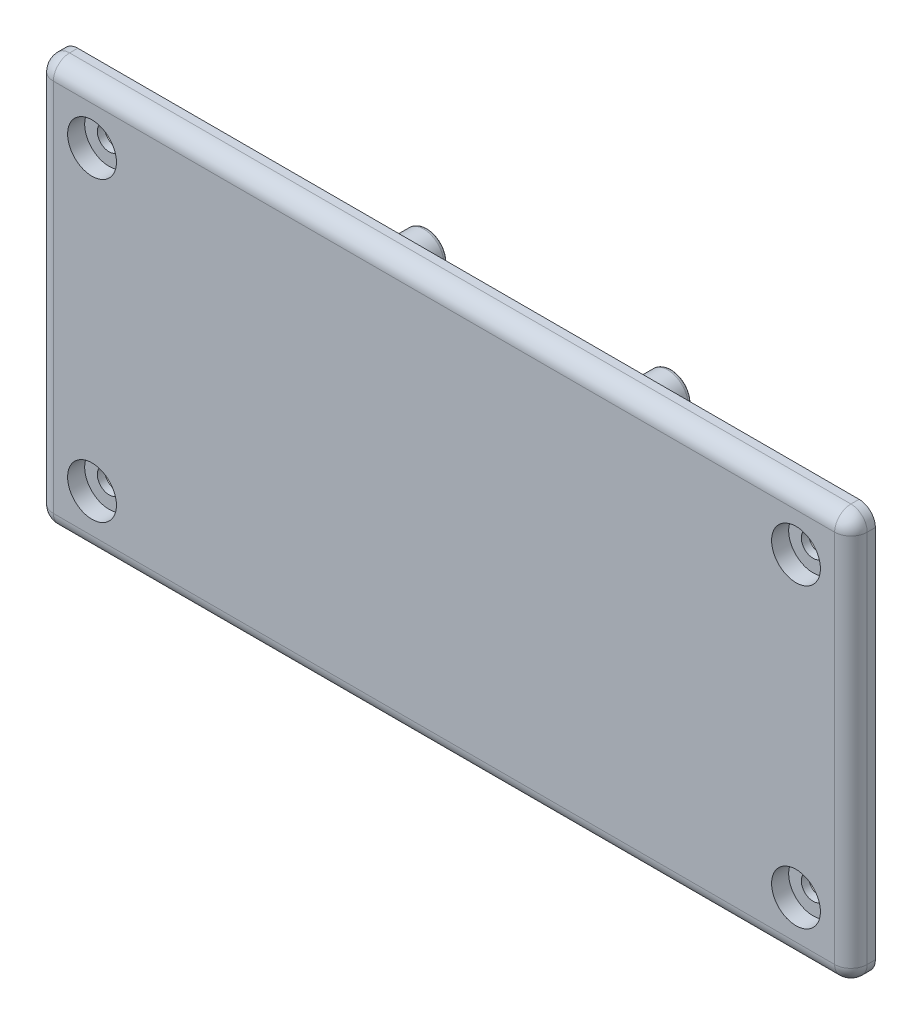
SolidWorks part; units mm, degrees
ref_plane "Front Plane" through (0, 0, 0) normal (0, 0, 1) x (1, 0, 0)
ref_plane "Top Plane" through (0, 0, 0) normal (0, 1, 0) x (1, 0, 0)
ref_plane "Right Plane" through (0, 0, 0) normal (1, 0, 0) x (0, 0, -1)
sketch "Sketch1" plane through (0, 0, 0) normal (0, 0, 1) x (1, 0, 0)
  line L4 (-48, -25) -> (48, -25)
  line L5 (50, -23) -> (50, 23)
  line L6 (48, 25) -> (-48, 25)
  line L7 (-50, 23) -> (-50, -23)
  line L8 (-48, -25) -> (48, -25)
  line L9 (50, -23) -> (50, 23)
  line L10 (48, 25) -> (-48, 25)
  line L11 (-50, 23) -> (-50, -23)
  arc A4 (48, -25) -> (50, -23) centre (48, -23) ccw
  arc A5 (50, 23) -> (48, 25) centre (48, 23) ccw
  arc A6 (-48, 25) -> (-50, 23) centre (-48, 23) ccw
  arc A7 (-50, -23) -> (-48, -25) centre (-48, -23) ccw
  arc A8 (48, -25) -> (50, -23) centre (48, -23) ccw
  arc A9 (50, 23) -> (48, 25) centre (48, 23) ccw
  arc A10 (-48, 25) -> (-50, 23) centre (-48, 23) ccw
  arc A11 (-50, -23) -> (-48, -25) centre (-48, -23) ccw
  dimension "D1" = 0
extrude "Boss-Extrude1" add sketch "Sketch1" along normal blind 3
fillet "Fillet1" radius 2 8 edges at (-50, 0, 3) (-49.4142, 24.4142, 3) (0, 25, 3) (49.4142, 24.4142, 3) (50, 0, 3) (49.4142, -24.4142, 3) (0, -25, 3) (-49.4142, -24.4142, 3)
sketch "Sketch2" plane through (0, 0, 0) normal (0, 0, -1) x (-1, 0, 0)
  line L0 (-25, -18.5) -> (-25, -21.5)
  line L1 (-35, -18.5) -> (-35, -21.5)
  line L2 (25, -18.5) -> (25, -21.5)
  line L3 (35, -18.5) -> (35, -21.5)
  line L4 (50, -23) -> (50, 23)
  line L5 (48, 25) -> (-48, 25)
  line L6 (-50, 23) -> (-50, -23)
  line L7 (-48, -25) -> (48, -25)
  line L8 (50, -23) -> (50, 23)
  line L9 (48, 25) -> (-48, 25)
  line L10 (-50, 23) -> (-50, -23)
  line L11 (-48, -25) -> (48, -25)
  line L12 (50, -23) -> (50, 23)
  line L13 (48, 25) -> (-48, 25)
  line L14 (-50, 23) -> (-50, -23)
  line L15 (-48, -25) -> (48, -25)
  line L16 (50, -23) -> (50, 23)
  line L17 (48, 25) -> (-48, 25)
  line L18 (-50, 23) -> (-50, -23)
  line L19 (-48, -25) -> (48, -25)
  line L20 (25, 18.5) -> (25, 21.5)
  line L21 (35, 18.5) -> (35, 21.5)
  line L22 (43.5, -10) -> (46.5, -10)
  line L23 (43.5, 10) -> (46.5, 10)
  line L24 (-46.5, -21.5) -> (46.5, -21.5)
  line L25 (-46.5, 21.5) -> (-46.5, -21.5)
  line L26 (46.5, 21.5) -> (-46.5, 21.5)
  line L27 (46.5, -21.5) -> (46.5, 21.5)
  line L28 (-46.5, -21.5) -> (46.5, -21.5)
  line L29 (-46.5, 21.5) -> (-46.5, -21.5)
  line L30 (46.5, 21.5) -> (-46.5, 21.5)
  line L31 (46.5, -21.5) -> (46.5, 21.5)
  line L32 (43.5, -18.5) -> (43.5, 18.5)
  line L33 (43.5, 18.5) -> (-43.5, 18.5)
  line L34 (-43.5, 18.5) -> (-43.5, -18.5)
  line L35 (-43.5, -18.5) -> (43.5, -18.5)
  line L36 (-43.5, -10) -> (-43.5, 10)
  line L37 (-25, 18.5) -> (-35, 18.5)
  line L38 (-43.5, 10) -> (-46.5, 10)
  line L39 (-43.5, 10) -> (-43.5, -10)
  line L40 (-43.5, -10) -> (-46.5, -10)
  line L41 (-46.5, 10) -> (-46.5, -10)
  line L42 (43.5, 0) -> (-46.5, 0) construction
  line L43 (-25, 18.5) -> (-35, 18.5)
  line L44 (-25, 18.5) -> (-25, 21.5)
  line L45 (-25, 21.5) -> (-35, 21.5)
  line L46 (-35, 18.5) -> (-35, 21.5)
  line L47 (0, 18.5) -> (0, -18.5) construction
  arc A4 (48, -25) -> (50, -23) centre (48, -23) ccw
  arc A5 (50, 23) -> (48, 25) centre (48, 23) ccw
  arc A6 (-48, 25) -> (-50, 23) centre (-48, 23) ccw
  arc A7 (-50, -23) -> (-48, -25) centre (-48, -23) ccw
  arc A8 (48, -25) -> (50, -23) centre (48, -23) ccw
  arc A9 (50, 23) -> (48, 25) centre (48, 23) ccw
  arc A10 (-48, 25) -> (-50, 23) centre (-48, 23) ccw
  arc A11 (-50, -23) -> (-48, -25) centre (-48, -23) ccw
  arc A12 (50, 23) -> (48, 25) centre (48, 23) ccw
  arc A13 (-48, 25) -> (-50, 23) centre (-48, 23) ccw
  arc A14 (-50, -23) -> (-48, -25) centre (-48, -23) ccw
  arc A15 (48, -25) -> (50, -23) centre (48, -23) ccw
  arc A16 (50, 23) -> (48, 25) centre (48, 23) ccw
  arc A17 (-48, 25) -> (-50, 23) centre (-48, 23) ccw
  arc A18 (-50, -23) -> (-48, -25) centre (-48, -23) ccw
  arc A19 (48, -25) -> (50, -23) centre (48, -23) ccw
  point P24 (-43.5, 0)
  point P29 (-30, 18.5)
  dimension "D5" = 20
  dimension "D6" = 10
  dimension "D7" = 11.5
  dimension "D1" = 0
  dimension "D2" = 0
  dimension "D3" = 3.5
  dimension "D4" = 3
extrude "Boss-Extrude2" add sketch "Sketch2" along normal blind 1.5 contours L46 L33 L44 L30 | L40 L34 L38 L29 | L35 L1 L28 L0 | L35 L2 L28 L3 | L32 L22 L31 L23 | L33 L21 L30 L20 region at (30, -20, 0) region at (-30, -20, 0) region at (45, 0, 0) region at (-45, 0, 0) region at (30, 20, 0) region at (-30, 20, 0)
fillet "Fillet2" radius 1 48 edges at (-25, 20, -1.5) (-30, 21.5, -1.5) (-35, 20, -1.5) (-30, 18.5, -1.5) (-35, -20, -1.5) (-30, -21.5, -1.5) (-25, -20, -1.5) (-30, -18.5, -1.5) (-45, 10, -1.5) (-46.5, 0, -1.5) (-45, -10, -1.5) (-43.5, 0, -1.5) (25, -20, -1.5) (30, -21.5, -1.5) (35, -20, -1.5) (30, -18.5, -1.5) (46.5, 0, -1.5) (45, 10, -1.5) (43.5, 0, -1.5) (45, -10, -1.5) (30, 21.5, -1.5) (25, 20, -1.5) (30, 18.5, -1.5) (35, 20, -1.5) (-25, 21.5, -0.75) (-35, 21.5, -0.75) (-35, 18.5, -0.75) (-25, 18.5, -0.75) (-25, -18.5, -0.75) (-25, -21.5, -0.75) (-35, -21.5, -0.75) (-35, -18.5, -0.75) (-46.5, -10, -0.75) (-43.5, -10, -0.75) (-46.5, 10, -0.75) (-43.5, 10, -0.75) (25, -18.5, -0.75) (25, -21.5, -0.75) (35, -18.5, -0.75) (35, -21.5, -0.75) (25, 21.5, -0.75) (25, 18.5, -0.75) (35, 21.5, -0.75) (35, 18.5, -0.75) (43.5, 10, -0.75) (46.5, 10, -0.75) (46.5, -10, -0.75) (43.5, -10, -0.75)
sketch "Sketch3" plane through (0, 0, 0) normal (0, 0, -1) x (-1, 0, 0)
  line L4 (50, -23) -> (50, 23)
  line L5 (48, 25) -> (-48, 25)
  line L6 (-50, 23) -> (-50, -23)
  line L7 (-48, -25) -> (48, -25)
  line L8 (50, -23) -> (50, 23)
  line L9 (48, 25) -> (-48, 25)
  line L10 (-50, 23) -> (-50, -23)
  line L11 (-48, -25) -> (48, -25)
  circle A0 centre (-15, -15) radius 3.0099 construction
  circle A1 centre (-15, 15) radius 3.0099 construction
  circle A2 centre (15, -15) radius 3.0099 construction
  circle A3 centre (15, 15) radius 3.0099 construction
  arc A4 (48, -25) -> (50, -23) centre (48, -23) ccw
  arc A5 (50, 23) -> (48, 25) centre (48, 23) ccw
  arc A6 (-48, 25) -> (-50, 23) centre (-48, 23) ccw
  arc A7 (-50, -23) -> (-48, -25) centre (-48, -23) ccw
  arc A8 (48, -25) -> (50, -23) centre (48, -23) ccw
  arc A9 (50, 23) -> (48, 25) centre (48, 23) ccw
  arc A10 (-48, 25) -> (-50, 23) centre (-48, 23) ccw
  arc A11 (-50, -23) -> (-48, -25) centre (-48, -23) ccw
  circle A12 centre (-15, -15) radius 3.0099 construction
  circle A13 centre (-15, 15) radius 3.0099 construction
  circle A14 centre (15, -15) radius 3.0099 construction
  circle A15 centre (15, 15) radius 3.0099 construction
  circle A16 centre (-15, 15) radius 2.5099
  circle A17 centre (-15, -15) radius 2.5099
  circle A18 centre (15, -15) radius 2.5099
  circle A19 centre (15, 15) radius 2.5099
  dimension "D1" = 0
  dimension "D2" = 0.5
extrude "Boss-Extrude3" add sketch "Sketch3" along normal blind 10 contours A17 | A16 | A18 | A19 region at (15, 15, 0) region at (15, -15, 0) region at (-15, -15, 0) region at (-15, 15, 0)
fillet "Fillet3" radius 0.5 4 edges at (12.4901, 15, -10) (-17.5099, -15, -10) (-17.5099, 15, -10) (12.4901, -15, -10)
sketch "Sketch4" plane through (0, 0, 3) normal (0, 0, 1) x (1, 0, 0)
  line L0 (-47, 14.5) -> (-39.5001, 14.5) construction
  line L1 (-39.5001, 22) -> (-39.5001, 14.5) construction
  line L2 (47, -14.5) -> (39.5001, -14.5) construction
  line L3 (39.5001, -22) -> (39.5001, -14.5) construction
  line L4 (48, 23) -> (-48, 23)
  line L5 (-48, 23) -> (-48, -23)
  line L6 (-48, -23) -> (48, -23)
  line L7 (48, -23) -> (48, 23)
  line L8 (48, 23) -> (-48, 23)
  line L9 (-48, 23) -> (-48, -23)
  line L10 (-48, -23) -> (48, -23)
  line L11 (48, -23) -> (48, 23)
  line L12 (-47, -22) -> (47, -22)
  line L13 (47, -22) -> (47, 22)
  line L14 (47, 22) -> (-47, 22)
  line L15 (-47, 22) -> (-47, -22)
  line L16 (-47, -22) -> (47, -22)
  line L17 (47, -22) -> (47, 22)
  line L18 (47, 22) -> (-47, 22)
  line L19 (-47, 22) -> (-47, -22)
  line L20 (47, 14.5) -> (39.5001, 14.5) construction
  line L21 (39.5001, 22) -> (39.5001, 14.5) construction
  line L22 (47, 0) -> (-47, 0) construction
  line L23 (0, -22) -> (0, 22) construction
  line L24 (-47, -14.5) -> (-39.5001, -14.5) construction
  line L25 (-39.5001, -22) -> (-39.5001, -14.5) construction
  line L26 (-47, 14.5) -> (-39.5001, 14.5)
  line L27 (-39.5001, 22) -> (-39.5001, 14.5)
  line L28 (47, -14.5) -> (39.5001, -14.5)
  line L29 (39.5001, -22) -> (39.5001, -14.5)
  line L30 (47, 14.5) -> (39.5001, 14.5)
  line L31 (39.5001, 22) -> (39.5001, 14.5)
  line L32 (47, 0) -> (-47, 0)
  line L33 (0, -22) -> (0, 22)
  line L34 (-47, -14.5) -> (-39.5001, -14.5)
  line L35 (-39.5001, -22) -> (-39.5001, -14.5)
  circle A1 centre (-43.2501, -18.25) radius 1.025
  circle A2 centre (-43.2501, -18.25) radius 1.025
  circle A3 centre (43.2501, -18.25) radius 1.025
  circle A4 centre (43.2501, -18.25) radius 1.025
  circle A5 centre (43.2501, 18.25) radius 1.025
  circle A6 centre (43.2501, 18.25) radius 1.025
  circle A7 centre (-43.2501, 18.25) radius 1.025
  circle A8 centre (-43.2501, 18.25) radius 1.025
  dimension "D1" = 0
  dimension "D2" = 0
  dimension "D3" = 0
  dimension "D4" = 0
  dimension "D5" = 0
  dimension "D6" = 0
hole_wizard "CBORE for M2.5 Pan Head Machine Screw1" positions "3DSketch2" profile "Sketch6" counterbore size "M2.5" standard "ANSI Metric"
sketch3d "3DSketch2"
  point P0 (43.2501, -18.25, 3)
  point P3 (43.2501, 18.25, 3)
  point P6 (-43.2501, -18.25, 3)
  point P9 (-43.2501, 18.25, 3)
sketch "Sketch6" plane through (43.2501, -18.25, 3) normal (1, 0, 0) x (0, -1, 0)
  line L0 (0, 0) -> (0, 7.2212)
  line L1 (0, 7.2212) -> (1.45, 6.35)
  line L2 (1.45, 6.35) -> (1.45, 2.1)
  line L3 (1.45, 2.1) -> (3, 2.1)
  line L4 (3, 2.1) -> (3, 0)
  line L5 (3, 0) -> (0, 0)
  line L10 (0, 7.2212) -> (-1.45, 6.35) construction
  line L11 (0, -6.35) -> (0, 107.95) construction
  dimension "Hole Dia." = 2.9
  dimension "Hole Depth" = 6.35
  dimension "C'Bore Dia." = 6
  dimension "C'Bore Depth" = 2.1
  dimension "Drill Angle" = 118
